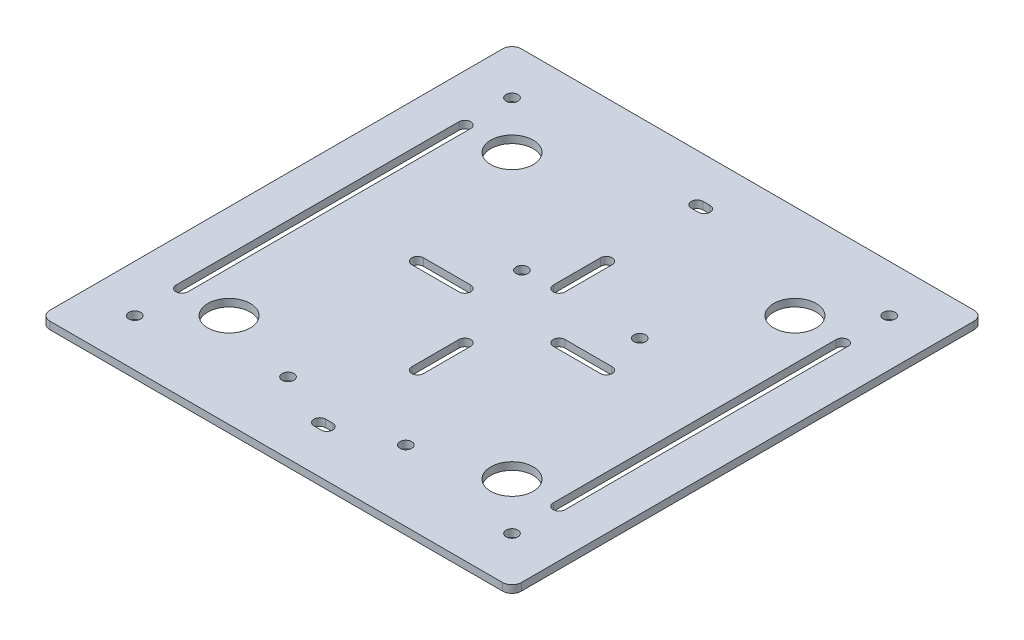
SolidWorks part; units mm, degrees
material "6061 Alloy"
ref_plane "Front Plane" through (0, 0, 0) normal (0, 0, 1) x (1, 0, 0)
ref_plane "Top Plane" through (0, 0, 0) normal (0, 1, 0) x (1, 0, 0)
ref_plane "Right Plane" through (0, 0, 0) normal (1, 0, 0) x (0, 0, -1)
sketch "Sketch2" plane through (0, 0, 0) normal (0, 1, 0) x (1, 0, 0)
  line L1 (0, 0) -> (100, 0)
  line L2 (0, 0) -> (0, 100)
  line L3 (0, 100) -> (100, 100)
  line L4 (100, 0) -> (100, 100)
  point P5 (50, 50)
  dimension "D1" = 100
  dimension "D2" = 50
  dimension "D3" = 50
extrude "Boss-Extrude1" add sketch "Sketch2" along normal blind 1.5875 contours L3 L4 L1 L2
sketch "Sketch3" plane through (0, 1.5875, 0) normal (0, 1, 0) x (1, 0, 0)
  line L0 (10, 80) -> (10, 20) construction
  line L1 (11.25, 80) -> (11.25, 20)
  line L2 (8.75, 80) -> (8.75, 20)
  line L5 (0, 100) -> (100, 100) construction
  line L6 (0, 0) -> (0, 100) construction
  arc A0 (11.25, 80) -> (8.75, 80) centre (10, 80) ccw
  arc A1 (8.75, 20) -> (11.25, 20) centre (10, 20) ccw
  point P2 (10, 50)
  dimension "D1" = 2.5
  dimension "D2" = 60
  dimension "D3" = 50
  dimension "D4" = 10
extrude "Cut-Extrude1" cut sketch "Sketch3" against normal blind 5 contours L1 A1 L2 A0
sketch "Sketch4" plane through (0, 1.5875, 0) normal (0, 1, 0) x (1, 0, 0)
  line L0 (0, 0) -> (0, 100) construction
  line L1 (0, 0) -> (100, 0) construction
  circle A0 centre (10, 10) radius 1.25
  dimension "D1" = 2.5
  dimension "D2" = 10
  dimension "D3" = 10
extrude "Cut-Extrude2" cut sketch "Sketch4" against normal blind 5
sketch "Sketch6" plane through (0, 1.5875, 0) normal (0, 1, 0) x (1, 0, 0)
  line L0 (49.25, 10) -> (50.75, 10) construction
  line L1 (49.25, 11.25) -> (50.75, 11.25)
  line L2 (49.25, 8.75) -> (50.75, 8.75)
  line L3 (0, 0) -> (100, 0) construction
  line L4 (0, 0) -> (0, 100) construction
  arc A0 (49.25, 11.25) -> (49.25, 8.75) centre (49.25, 10) ccw
  arc A1 (50.75, 8.75) -> (50.75, 11.25) centre (50.75, 10) ccw
  point P2 (50, 10)
  dimension "D2" = 1.25
  dimension "D1" = 1.5
  dimension "D3" = 10
  dimension "D4" = 50
extrude "Cut-Extrude4" cut sketch "Sketch6" against normal blind 5
sketch "Sketch8" plane through (0, 1.5875, 0) normal (0, 1, 0) x (1, 0, 0)
  line L0 (30, 50) -> (40, 50) construction
  line L1 (30, 51.25) -> (40, 51.25)
  line L2 (30, 48.75) -> (40, 48.75)
  line L3 (0, 0) -> (100, 0) construction
  line L4 (0, 0) -> (0, 100) construction
  arc A0 (30, 51.25) -> (30, 48.75) centre (30, 50) ccw
  arc A1 (40, 48.75) -> (40, 51.25) centre (40, 50) ccw
  point P2 (35, 50)
  dimension "D1" = 2.5
  dimension "D2" = 10
  dimension "D3" = 50
  dimension "D4" = 40
extrude "Cut-Extrude6" cut sketch "Sketch8" against normal blind 5 contours L1 A1 L2 A0
ref_plane "Plane1" through (50, 0, 0) normal (1, 0, 0) x (0, 0, -1)
ref_plane "Plane2" through (0, 0, -50) normal (0, 0, -1) x (-1, 0, 0)
ref_axis "Axis1" through (50, -0.2, -50) along (0, 1, 0)
mirror "Mirror3" about plane through (50, 0, 0) normal (1, 0, 0) of "Cut-Extrude1"
pattern_circular "CirPattern1" count 4 over 360 about axis through (50, -0.2, -50) along (0, 1, 0) of "Cut-Extrude6"
pattern_circular "CirPattern4" count 4 over 360 about axis through (50, -0.2, -50) along (0, 1, 0) of "Cut-Extrude2"
mirror "Mirror6" about plane through (0, 0, -50) normal (0, 0, -1) of "Cut-Extrude4"
fillet "Fillet2" radius 2 4 edges at (100, 0.7937, 0) (0, 0.7937, 0) (0, 0.7937, -100) (100, 0.7937, -100)
hole_wizard "Ø2.5mm Dowel Hole1" positions "Sketch9" profile "Sketch10" hole size "Ø2.5" standard "ANSI Metric" end condition through all
sketch "Sketch9" plane through (0, 1.5875, 0) normal (0, 1, 0) x (1, 0, 0)
  point P0 (62.5, 15)
  point P2 (37.5, 15)
  dimension "D1" = 35
  dimension "D2" = 35
  dimension "D3" = 25
  dimension "D4" = 12.5
sketch "Sketch10" plane through (62.5, 1.5875, -15) normal (1, 0, 0) x (0, 0, 1)
  line L0 (0, 0) -> (0, 1.5875)
  line L1 (0, 1.5875) -> (1.25, 1.5875)
  line L2 (1.25, 1.5875) -> (1.25, 0)
  line L5 (1.25, 0) -> (0, 0)
  line L11 (0, -6.35) -> (0, 107.95) construction
  dimension "Thru Hole Dia." = 2.5
  dimension "Thru Hole Depth" = 1.5875
hole_wizard "Ø2.5mm Dowel Hole2" positions "Sketch11" profile "Sketch12" hole size "Ø2.5" standard "ANSI Metric" end condition through all
sketch "Sketch11" plane through (0, 1.5875, 0) normal (0, 1, 0) x (1, 0, 0)
  point P0 (42.7, 59.4)
  point P2 (67.7, 59.4)
  dimension "D1" = 9.4
  dimension "D2" = 9.4
  dimension "D3" = 25
  dimension "D4" = 7.3
sketch "Sketch12" plane through (42.7, 1.5875, -59.4) normal (1, 0, 0) x (0, 0, 1)
  line L0 (0, 0) -> (0, 1.5875)
  line L1 (0, 1.5875) -> (1.25, 1.5875)
  line L2 (1.25, 1.5875) -> (1.25, 0)
  line L5 (1.25, 0) -> (0, 0)
  line L11 (0, -6.35) -> (0, 107.95) construction
  dimension "Thru Hole Dia." = 2.5
  dimension "Thru Hole Depth" = 1.5875
hole_wizard "Ø9.0 (9) Diameter Hole1" positions "Sketch13" profile "Sketch14" hole size "Ø9.0" standard "ANSI Metric" end condition through all
sketch "Sketch13" plane through (0, 1.5875, 0) normal (0, 1, 0) x (1, 0, 0)
  line L0 (100, 2) -> (100, 98) construction
  line L1 (2, 0) -> (98, 0) construction
  point P0 (80, 20)
  dimension "D1" = 20
  dimension "D2" = 20
sketch "Sketch14" plane through (80, 1.5875, -20) normal (1, 0, 0) x (0, 0, 1)
  line L0 (0, 0) -> (0, 1.5875)
  line L1 (0, 1.5875) -> (4.5, 1.5875)
  line L2 (4.5, 1.5875) -> (4.5, 0)
  line L5 (4.5, 0) -> (0, 0)
  line L11 (0, -6.35) -> (0, 107.95) construction
  dimension "Thru Hole Dia." = 9
  dimension "Thru Hole Depth" = 1.5875
pattern_circular "CirPattern5" count 4 over 360 about axis through (50, -0.2, -50) along (0, 1, 0) of "Ø9.0 (9) Diameter Hole1"
